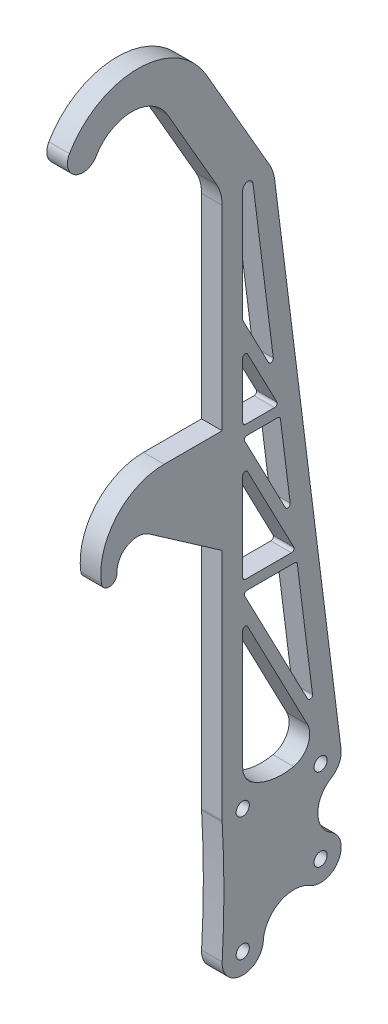
SolidWorks part; units mm, degrees
ref_plane "Front Plane" through (0, 0, 0) normal (0, 0, 1) x (1, 0, 0)
ref_plane "Top Plane" through (0, 0, 0) normal (0, 1, 0) x (1, 0, 0)
ref_plane "Right Plane" through (0, 0, 0) normal (1, 0, 0) x (0, 0, -1)
sketch "Sketch1" plane through (0, 0, 0) normal (1, 0, 0) x (0, 0, -1)
  line L1 (12.0015, 19.05) -> (12.0015, -6.35) construction
  line L2 (-12.0015, -19.05) -> (-12.0015, 19.05) construction
  line L3 (12.0015, 0) -> (-12.0015, 0) construction
  line L4 (-6.35, 19.05) -> (6.35, 19.05) construction
  line L5 (-18.3515, 19.05) -> (-18.3515, 183.3563)
  line L6 (8.7396, -11.7982) -> (-4.7505, -3.7215) construction
  line L7 (18.3016, 19.8442) -> (-2.4765, 184.6629)
  line L8 (-12.0015, 25.4) -> (-12.0015, 69.85)
  line L9 (-57.173, 215.9) -> (-72.296, 189.7062) construction
  line L10 (-61.2974, 170.6563) -> (-31.0515, 170.6563) construction
  line L11 (-20.053, 189.7062) -> (-35.1759, 215.9)
  line L12 (-46.1745, 209.55) -> (-61.2974, 183.3562) construction
  line L13 (-61.2974, 183.3562) -> (-31.0515, 183.3562) construction
  line L14 (-31.0515, 183.3562) -> (-46.1745, 209.55) construction
  line L15 (-23.2609, 220.6625) -> (-2.4765, 184.6629)
  line L16 (-2.4765, 184.6629) -> (-13.475, 178.3129) construction
  line L17 (-57.173, 215.9) -> (-65.4219, 220.6625) construction
  line L18 (15.2634, -0.9018) -> (7.7798, 3.5787) construction
  line L19 (-12.0015, 69.85) -> (11.2073, 25.3501)
  line L20 (11.2073, 25.3501) -> (-0.8823, 121.2482) construction
  line L21 (8.7396, 24.4982) -> (1.1915, 19.979) construction
  line L22 (15.2634, 13.6018) -> (8.3747, 9.4775) construction
  line L23 (10.0658, 34.4046) -> (-12.0015, 76.7159)
  line L24 (-12.0015, 76.7159) -> (4.7318, 76.7159)
  line L25 (4.7318, 76.7159) -> (10.0658, 34.4046)
  line L26 (4.3315, 79.8909) -> (-12.0015, 79.8909)
  line L27 (-12.0015, 79.8909) -> (-12.0015, 111.2073)
  line L28 (-12.0015, 111.2073) -> (4.3315, 79.8909)
  line L29 (3.19, 88.9454) -> (-12.0015, 118.0732)
  line L30 (-12.0015, 118.0732) -> (-0.482, 118.0732)
  line L31 (-0.482, 118.0732) -> (3.19, 88.9454)
  line L32 (-0.8823, 121.2482) -> (-12.0015, 121.2482)
  line L33 (-12.0015, 121.2482) -> (-12.0015, 142.5679)
  line L34 (-8.839, 184.3631) -> (-2.0238, 130.3027)
  line L35 (-12.0015, 69.85) -> (-9.1864, 71.3182) construction
  line L36 (-12.0015, 76.7159) -> (-12.0015, 79.8909) construction
  line L37 (-12.0015, 111.2073) -> (-9.1864, 112.6755) construction
  line L38 (-12.0015, 118.0732) -> (-12.0015, 121.2482) construction
  line L39 (-0.8823, 121.2482) -> (-12.0015, 142.5679)
  line L40 (-2.0238, 130.3027) -> (-12.0015, 149.4338)
  line L41 (-12.0015, 142.5679) -> (-9.1864, 144.0361) construction
  line L42 (-2.0238, 130.3027) -> (-1.5228, 126.3291) construction
  line L43 (-12.0015, 149.4338) -> (-12.0015, 184.1645)
  line L44 (-18.3408, -18.6818) -> (-16.9094, 5.9637) construction
  line L45 (-5.6622, -19.4182) -> (-4.7505, -3.7215) construction
  circle A0 centre (-12.0015, 19.05) radius 5.6515 construction
  circle A1 centre (12.0015, 19.05) radius 5.6515 construction
  arc A2 (-18.3408, -18.6818) -> (-5.6622, -19.4182) centre (-12.0015, -19.05) ccw
  arc A3 (8.7396, -11.7982) -> (15.2634, -0.9018) centre (12.0015, -6.35) ccw
  arc A4 (15.2634, 13.6018) -> (18.3016, 19.8442) centre (12.0015, 19.05) ccw
  arc A5 (15.2634, 13.6018) -> (15.2634, -0.9018) centre (19.6051, 6.35) ccw
  arc A7 (-35.1759, 215.9) -> (-57.173, 215.9) centre (-46.1745, 209.55) ccw
  arc A8 (-72.296, 189.7062) -> (-61.2974, 170.6563) centre (-61.2974, 183.3562) ccw construction
  arc A9 (-31.0515, 170.6563) -> (-20.053, 189.7062) centre (-31.0515, 183.3562) ccw construction
  circle A10 centre (-46.1745, 192.0875) radius 8.7312 construction
  arc A11 (-18.3515, 183.3563) -> (-20.053, 189.7062) centre (-31.0515, 183.3563) ccw
  arc A12 (-57.173, 215.9) -> (-65.4219, 220.6625) centre (-61.2974, 218.2813) cw
  arc A13 (-65.4219, 220.6625) -> (-23.2609, 220.6625) centre (-44.3414, 208.4917) cw
  arc A14 (-5.6622, -19.4182) -> (8.7396, -11.7982) centre (3.8468, -19.9704) cw
  arc A15 (-12.0015, 25.4) -> (-8.7396, 24.4982) centre (-12.0015, 19.05) cw
  arc A17 (11.2073, 25.3501) -> (8.7396, 24.4982) centre (12.0015, 19.05) ccw
  arc A18 (8.7396, 24.4982) -> (-8.7396, 24.4982) centre (0, 39.0956) cw
  arc A19 (-12.0015, 184.1645) -> (-8.839, 184.3631) centre (-10.414, 184.1645) cw
  arc A20 (-18.3515, 19.05) -> (-18.3408, 18.6818) centre (-12.0015, 19.05) ccw
  arc A21 (-18.3408, -18.6818) -> (-18.3408, 18.6818) centre (-340.0076, 0) ccw
  point P11 (0, 0)
  point P47 (-12.0015, 0)
  point P48 (-46.1745, 222.25)
  dimension "D3" = 12.7
  dimension "D4" = 11.303
  dimension "D5" = 6.35
  dimension "D6" = 15.875
  dimension "D7" = 12.7
  dimension "D9" = 12.7
  dimension "D10" = 4.7625
  dimension "D12" = 6.35
  dimension "D14" = 3.175
  dimension "D15" = 1.5875
  dimension "D17" = 9.525
  dimension "D1" = 25.4
  dimension "D2" = 38.1
  dimension "D8" = 38.8937
  dimension "D11" = 222.25
  dimension "D13" = 6.35
  dimension "D16" = 44.45
extrude "Boss-Extrude1" add sketch "Sketch1" along normal mid plane 6.35
sketch "Sketch2" plane through (3.175, 0, 0) normal (1, 0, 0) x (0, 0, -1)
  line L0 (-12.0015, -19.05) -> (-12.0015, 19.05) construction
  circle A0 centre (12.0015, -6.35) radius 2.032
  circle A1 centre (12.0015, 19.05) radius 2.032
  circle A2 centre (-12.0015, 19.05) radius 2.032
  circle A3 centre (-12.0015, -19.05) radius 2.032
  dimension "D1" = 4.064
extrude "Cut-Extrude1" cut sketch "Sketch2" against normal through all
fillet "Fillet1" radius 12.7 1 edges at (0, 184.6629, 2.4765)
fillet "Fillet2" radius 0.7937 15 edges at (0, 121.2482, 12.0015) (0, 118.0732, 12.0015) (0, 118.0732, 0.482) (0, 88.9454, -3.19) (0, 111.2073, 12.0015) (0, 79.8909, 12.0015) (0, 79.8909, -4.3315) (0, 69.85, 12.0015) (0, 76.7159, 12.0015) (0, 76.7159, -4.7318) (0, 34.4046, -10.0658) (0, 149.4338, 12.0015) (0, 121.2482, 0.8823) (0, 142.5679, 12.0015) (0, 130.3027, 2.0238)
fillet "Fillet3" radius 6.35 2 edges at (0, 25.4, 12.0015) (0, 25.3501, -11.2073)
sketch "Sketch3" plane through (3.175, 0, 0) normal (1, 0, 0) x (0, 0, -1)
  line L1 (-18.3515, 183.3563) -> (-18.3515, 19.05) construction
  line L2 (-18.3515, 123.1465) -> (-18.3515, 91.1948)
  line L3 (-40.8261, 106.8144) -> (-18.3515, 91.1948)
  line L4 (-18.3515, 123.1465) -> (-36.2439, 123.1468)
  arc A0 (-40.8261, 106.8144) -> (-50.7947, 101.3405) centre (-44.45, 101.6) ccw
  arc A1 (-36.2439, 123.1468) -> (-55.5701, 100.9076) centre (-36.2442, 103.63) ccw
  arc A2 (-55.5701, 100.9076) -> (-50.7947, 101.3405) centre (-53.1932, 101.2425) ccw
  point P3 (-18.3515, 123.1468)
  dimension "D1" = 6.35
  dimension "D2" = 101.6
  dimension "D3" = 44.45
extrude "Boss-Extrude2" add sketch "Sketch3" against normal up to surface (6.35 mm away) up to face at (-3.175, -19.05, 9.9695)
